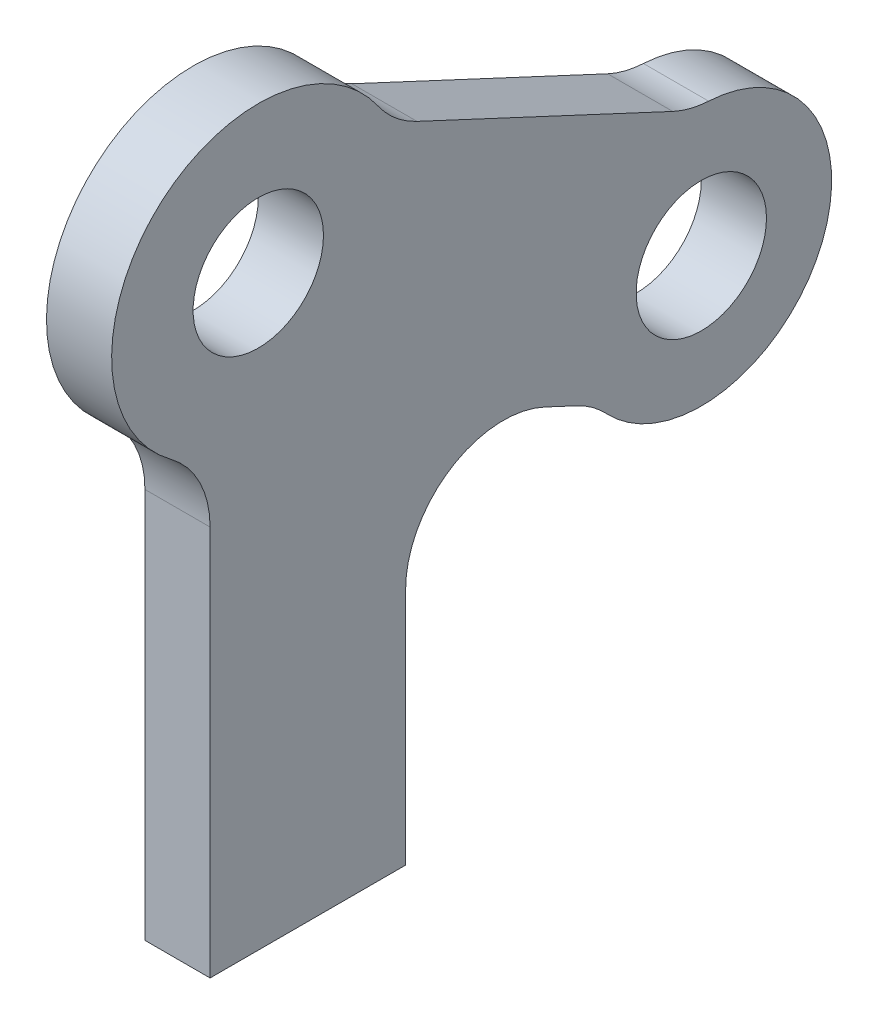
SolidWorks part; units mm, degrees
ref_plane "前视基准面" through (0, 0, 0) normal (0, 0, 1) x (1, 0, 0)
ref_plane "上视基准面" through (0, 0, 0) normal (0, 1, 0) x (1, 0, 0)
ref_plane "右视基准面" through (0, 0, 0) normal (1, 0, 0) x (0, 0, -1)
other "Configuration Table"
sketch "草图1" plane through (0, 0, 0) normal (1, 0, 0) x (0, 0, -1)
  line L1 (-1.4792, -3.1721) -> (4.5208, -3.1721)
  line L2 (-1.4792, -3.1721) -> (-1.4792, -18)
  line L3 (-1.4792, -18) -> (4.5208, -18)
  line L4 (4.5208, -3.1721) -> (4.5208, -18)
  line L5 (-1.4792, -3.1721) -> (12.1155, -9.5114)
  line L6 (-1.4792, -3.1721) -> (1.4792, 3.1721)
  line L7 (1.4792, 3.1721) -> (15.0738, -3.1672)
  line L8 (12.1155, -9.5114) -> (15.0738, -3.1672)
  circle A0 centre (0, 0) radius 4.5
  circle A1 centre (13.5946, -6.3393) radius 4
  circle A2 centre (0, 0) radius 2
  circle A3 centre (13.5946, -6.3393) radius 2
  dimension "D4" = 9
  dimension "D5" = 8
  dimension "D8" = 4
  dimension "D1" = 65
  dimension "D2" = 18
  dimension "D3" = 6
  dimension "D6" = 7
  dimension "D7" = 15
extrude "凸台-拉伸1" add sketch "草图1" along normal blind 2 contours L6 L7 L8 L5 | A0 | A1 | L1 L4 L3 L2
extrude "切除-拉伸3" cut sketch "草图1<3>" against normal through all and the other way through all contours A2 | A3
sketch "草图1<3>" plane through (0, 0, 0) normal (1, 0, 0) x (0, 0, -1) same geometry as "草图1"
fillet "圆角1" radius 3 5 edges at (1, -4.2499, 1.4792) (1, 1.9767, -4.0426) (1, -5.9699, -4.5208) (1, -8.693, -10.3604) (1, -2.3488, -13.3187)
equation "\"JointPoint\"= 2mm"
